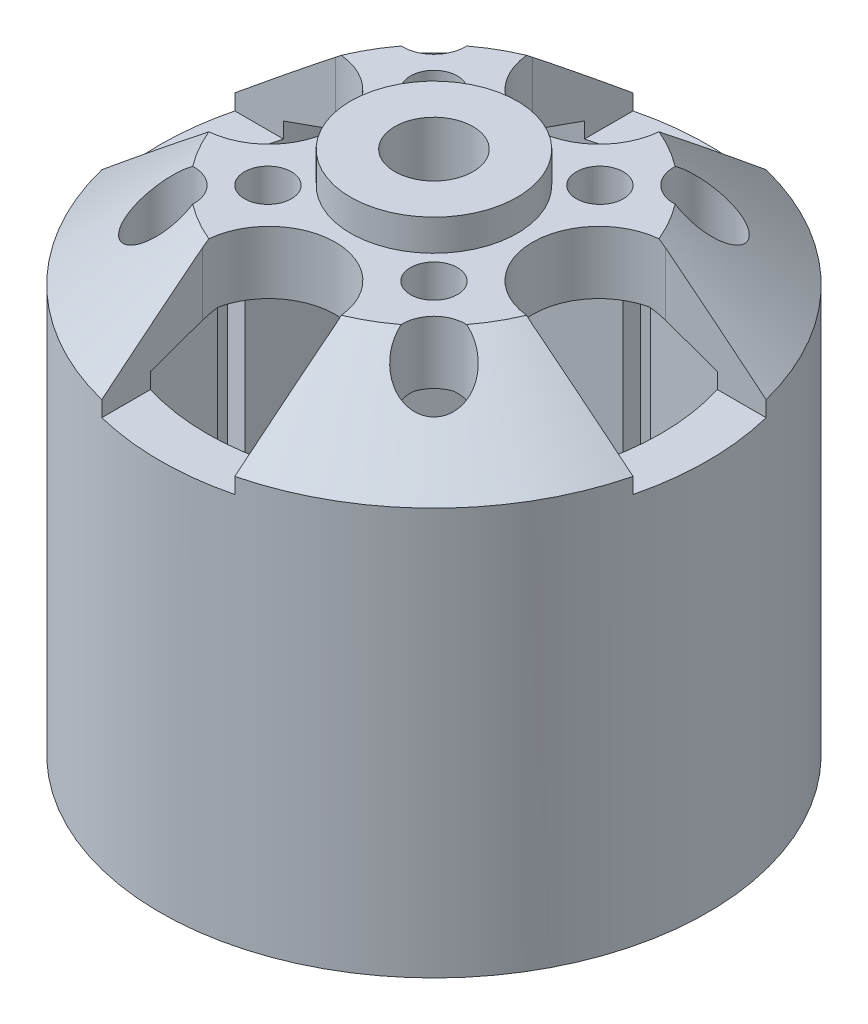
SolidWorks part; units mm, degrees
material "6061-T6 (SS)"
ref_plane "Front Plane" through (0, 0, 0) normal (0, 0, 1) x (1, 0, 0)
ref_plane "Top Plane" through (0, 0, 0) normal (0, 1, 0) x (1, 0, 0)
ref_plane "Right Plane" through (0, 0, 0) normal (1, 0, 0) x (0, 0, -1)
sketch "Sketch1" plane through (0, 0, 0) normal (0, 0, 1) x (1, 0, 0)
  line L0 (0, 0) -> (0, -4.7001) construction
  line L1 (17.5, 0) -> (17.5, 25)
  line L2 (17.5, 0) -> (0, 0)
  line L3 (17.5, 25) -> (17.5, 26)
  line L4 (17.5, 26) -> (11, 31.5)
  line L5 (11, 31.5) -> (5.325, 31.5)
  line L6 (5.325, 31.5) -> (5.325, 33.5)
  line L7 (5.325, 33.5) -> (0, 33.5)
  line L8 (0, 0) -> (0, 33.5)
  dimension "D1" = 35
  dimension "D2" = 25
  dimension "D3" = 10.65
  dimension "D4" = 2
  dimension "D5" = 1
  dimension "D6" = 6.5
  dimension "D7" = 22
revolve "Outer Profile" add sketch "Sketch1" angle 360 about L0
sketch "Sketch3" plane through (0, 0, 0) normal (0, 0, 1) x (1, 0, 0)
  line L0 (0, 0) -> (0, 36.7743) construction
  line L1 (16.5, 0) -> (16.5, 21)
  line L2 (-17.5, 0) -> (17.5, 0) construction
  line L3 (16.5, 21) -> (14.5, 21)
  line L4 (14.5, 21) -> (14.5, 26)
  line L5 (-17.5, 26) -> (17.5, 26) construction
  line L6 (14.5, 26) -> (10.5, 27.5)
  line L7 (10.5, 27.5) -> (5, 27.5)
  line L8 (5, 27.5) -> (3.5, 22.9)
  line L9 (3.5, 22.9) -> (2.5, 22.9)
  line L10 (2.5, 22.9) -> (2.5, 33.5)
  line L11 (5.325, 33.5) -> (-5.325, 33.5) construction
  line L12 (2.5, 33.5) -> (0, 33.5)
  line L13 (0, 33.5) -> (0, 0)
  line L14 (0, 0) -> (16.5, 0)
  line L15 (17.5, 26) -> (17.5, 0)
  line L16 (-17.5, 0) -> (-17.5, 26)
  line L17 (-17.5, 0) -> (-17.5, 26) construction
  line L18 (17.5, 26) -> (17.5, 0) construction
  line L19 (11, 31.5) -> (-11, 31.5) construction
  line L20 (-17.5, 26) -> (-11, 31.5)
  line L21 (11, 31.5) -> (17.5, 26)
  line L22 (11, 31.5) -> (17.5, 26) construction
  line L23 (-17.5, 26) -> (-11, 31.5) construction
  dimension "D1" = 5
  dimension "D2" = 1
  dimension "D3" = 3
  dimension "D4" = 5
  dimension "D5" = 4
  dimension "D6" = 0.5
  dimension "D7" = 10
  dimension "D8" = 1
  dimension "D9" = 10.6
revolve "Inner Profile" cut sketch "Sketch3" angle 360 about L0
ref_plane "Plane1" through (0, 25, 0) normal (0, 1, 0) x (1, 0, 0)
sketch "Sketch5" plane through (0, 25, 0) normal (0, 1, 0) x (1, 0, 0)
  line L0 (-4.25, 16.9761) -> (-4.25, 10.55)
  line L1 (4.25, 10.55) -> (4.25, 16.9761)
  line L2 (0, 10.55) -> (0, 0) construction
  line L3 (8.6621, 8.6621) -> (0, 0) construction
  arc A0 (-4.25, 16.9761) -> (4.25, 16.9761) centre (0, 0) cw
  circle A1 centre (0, 0) radius 17.5 construction
  arc A2 (-4.25, 10.55) -> (4.25, 10.55) centre (0, 10.55) ccw
  circle A3 centre (8.6621, 8.6621) radius 2
  circle A4 centre (5.3033, 5.3033) radius 1.5
  point P11 (0, 6.3)
  dimension "D4" = 4
  dimension "D6" = 3
  dimension "D1" = 8.5
  dimension "D2" = 6.3
  dimension "D3" = 45
  dimension "D5" = 12.25
  dimension "D7" = 7.5
extrude "Top Cuts" cut sketch "Sketch5" along normal through all
pattern_circular "Top Cuts Pattern" count 4 over 360 about axis through (0, 0, 0) along (0, -1, 0) of "Top Cuts"
sketch "Sketch6" plane through (0, 21, 0) normal (0, -1, 0) x (1, 0, 0)
  line L0 (9.7648, 13.3003) -> (8.4853, 12.0208)
  line L1 (8.4853, 12.0208) -> (12.0208, 8.4853)
  line L2 (12.0208, 8.4853) -> (13.3003, 9.7648)
  line L3 (10.253, 10.253) -> (0, 0) construction
  circle A0 centre (0, 0) radius 16.5 construction
  arc A1 (9.7648, 13.3003) -> (13.3003, 9.7648) centre (0, 0) cw
  circle A2 centre (5.3033, 5.3033) radius 1.5 construction
  circle A3 centre (5.3033, 5.3033) radius 1.5 construction
  circle A4 centre (0, 0) radius 17.5 construction
  point P13 (12.3744, 12.3744)
  dimension "D1" = 3
  dimension "D2" = 5
extrude "Magnet" add sketch "Sketch6" along normal offset from surface (19.5 mm away) 1.5 up to face at (0, 0, -16.5)
pattern_circular "Magnet Pattern" count 14 over 360 about axis through (0, 0, 0) along (0, -1, 0) of "Magnet" reverse direction yes
sketch "Sketch7" [suppressed] plane through (0, 25, 0) normal (0, 1, 0) x (1, 0, 0)
  circle A0 centre (0, 0) radius 17.5 construction
  circle A1 centre (0, 0) radius 17.5
extrude "Top Removal" [suppressed] cut sketch "Sketch7" along normal through all
